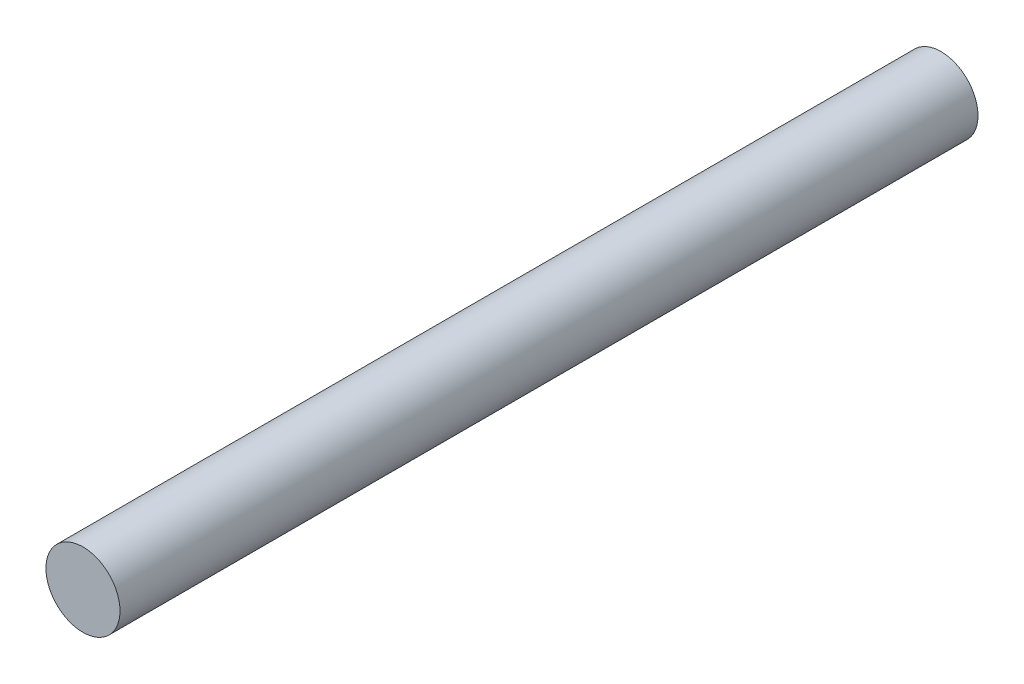
SolidWorks part; units mm, degrees
ref_plane "Front Plane" through (0, 0, 0) normal (0, 0, 1) x (1, 0, 0)
ref_plane "Top Plane" through (0, 0, 0) normal (0, 1, 0) x (1, 0, 0)
ref_plane "Right Plane" through (0, 0, 0) normal (1, 0, 0) x (0, 0, -1)
sketch "Sketch1" plane through (0, 0, 0) normal (0, 0, 1) x (1, 0, 0)
  circle A0 centre (0, 0) radius 6
  dimension "D1" = 12
extrude "Boss-Extrude1" add sketch "Sketch1" along normal blind 139
ref_plane "Plane1" through (0, 0, 69.5) normal (0, 0, 1) x (1, 0, 0)
ref_axis "Axis1" through (0, -6.6, 69.5) along (0, 1, 0)
